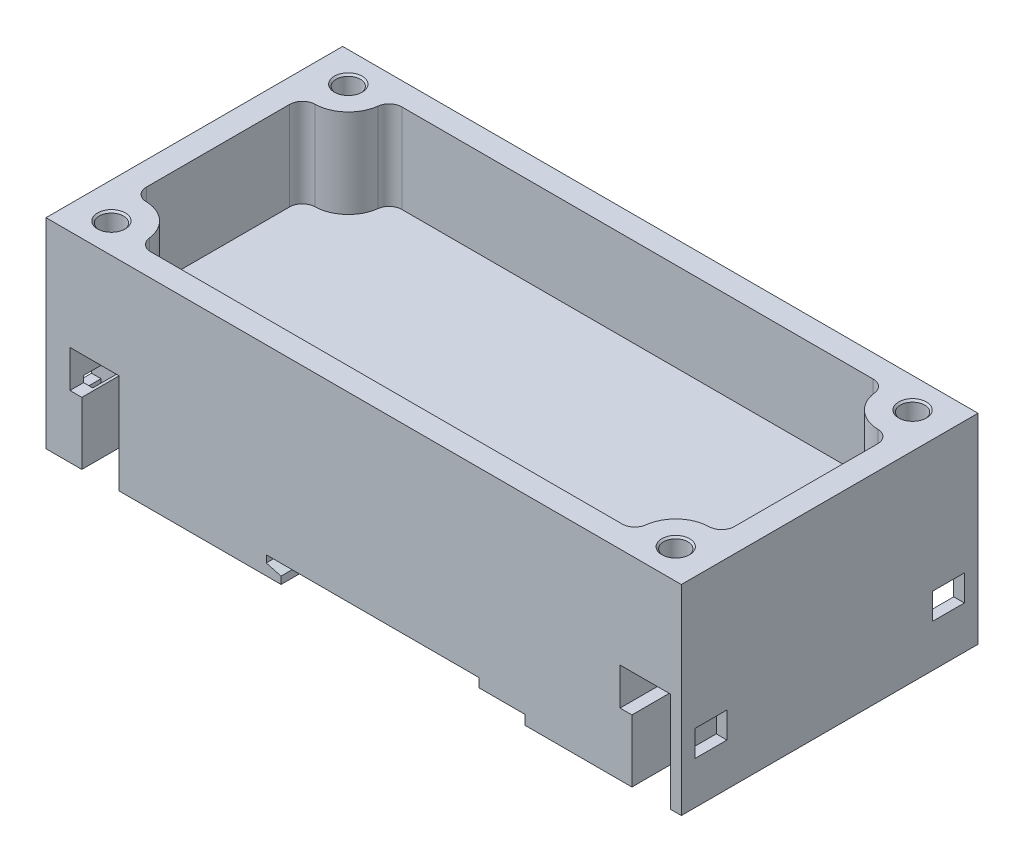
SolidWorks part; units mm, degrees
ref_plane "Front Plane" through (0, 0, 0) normal (0, 0, 1) x (1, 0, 0)
ref_plane "Top Plane" through (0, 0, 0) normal (0, 1, 0) x (1, 0, 0)
ref_plane "Right Plane" through (0, 0, 0) normal (1, 0, 0) x (0, 0, -1)
ref_plane "Plane1" through (0, 0, 0) normal (0, 0, 1) x (1, 0, 0)
sketch "Sketch1" plane through (0, 0, 0) normal (0, 0, 1) x (1, 0, 0)
  line L0 (-53.65, 33.8) -> (-53.65, 0)
  line L1 (-53.65, 0) -> (-47.6, 0)
  line L2 (-47.6, 0) -> (-47.6, 10.55)
  line L3 (-47.6, 10.55) -> (-49.6, 10.55)
  line L4 (-49.6, 10.55) -> (-49.6, 16.85)
  line L5 (-49.6, 16.85) -> (-41.3, 16.85)
  line L6 (-41.3, 16.85) -> (-41.3, 0)
  line L7 (-41.3, 0) -> (-13.95, 0)
  line L8 (-13.95, 0) -> (-13.95, 1.2301)
  line L9 (-13.95, 1.2301) -> (-16.45, 1.9)
  line L10 (-16.45, 1.9) -> (-16.45, 3.1)
  line L11 (-16.45, 3.1) -> (19.45, 3.1)
  line L12 (19.45, 3.1) -> (19.45, 1.6)
  line L13 (19.45, 1.6) -> (27.25, 1.6)
  line L14 (27.25, 1.6) -> (27.25, 0)
  line L15 (27.25, 0) -> (45.3, 0)
  line L16 (45.3, 0) -> (45.3, 10.55)
  line L17 (45.3, 10.55) -> (43.3, 10.55)
  line L18 (43.3, 10.55) -> (43.3, 16.85)
  line L19 (43.3, 16.85) -> (51.85, 16.85)
  line L20 (51.85, 16.85) -> (51.85, 0)
  line L21 (51.85, 0) -> (53.65, 0)
  line L22 (53.65, 0) -> (53.65, 33.8)
  line L23 (53.65, 33.8) -> (-53.65, 33.8)
extrude "Boss-Extrude1" add sketch "Sketch1" against normal blind 25.05 and the other way blind 25.05
ref_plane "Plane2" through (0, 0, 20) normal (0, 0, 1) x (1, 0, 0)
sketch "Sketch2" plane through (0, 0, 20) normal (0, 0, 1) x (1, 0, 0)
  line L0 (47.65, 33.8) -> (50, 33.8)
  line L1 (50, 33.8) -> (49.7, 33.5)
  line L2 (49.7, 33.5) -> (49.7, 26.6)
  line L3 (49.5, 26.4) -> (49.02, 26.4)
  line L4 (49.02, 26.4) -> (48.95, 18.4)
  line L5 (48.95, 18.4) -> (47.65, 18.4)
  line L6 (47.65, 18.4) -> (47.65, 33.8)
  line L7 (47.65, 18.4) -> (47.65, 33.8) construction
  arc A0 (49.7, 26.6) -> (49.5, 26.4) centre (49.5, 26.6) cw
revolve "Cut-Revolve1" cut sketch "Sketch2" angle 360 about L7 reverse direction yes
ref_plane "Plane3" through (0, 0, -20) normal (0, 0, 1) x (1, 0, 0)
sketch "Sketch3" plane through (0, 0, -20) normal (0, 0, 1) x (1, 0, 0)
  line L0 (47.65, 33.8) -> (50, 33.8)
  line L1 (50, 33.8) -> (49.7, 33.5)
  line L2 (49.7, 33.5) -> (49.7, 26.6)
  line L3 (49.5, 26.4) -> (49.02, 26.4)
  line L4 (49.02, 26.4) -> (48.95, 18.4)
  line L5 (48.95, 18.4) -> (47.65, 18.4)
  line L6 (47.65, 18.4) -> (47.65, 33.8)
  line L7 (47.65, 18.4) -> (47.65, 33.8) construction
  arc A0 (49.7, 26.6) -> (49.5, 26.4) centre (49.5, 26.6) cw
revolve "Cut-Revolve2" cut sketch "Sketch3" angle 360 about L7 reverse direction yes
ref_plane "Plane4" through (0, 0, -20) normal (0, 0, 1) x (1, 0, 0)
sketch "Sketch4" plane through (0, 0, -20) normal (0, 0, 1) x (1, 0, 0)
  line L0 (-47.65, 33.8) -> (-45.3, 33.8)
  line L1 (-45.3, 33.8) -> (-45.6, 33.5)
  line L2 (-45.6, 33.5) -> (-45.6, 26.6)
  line L3 (-45.8, 26.4) -> (-46.28, 26.4)
  line L4 (-46.28, 26.4) -> (-46.35, 18.4)
  line L5 (-46.35, 18.4) -> (-47.65, 18.4)
  line L6 (-47.65, 18.4) -> (-47.65, 33.8)
  line L7 (-47.65, 18.4) -> (-47.65, 33.8) construction
  arc A0 (-45.6, 26.6) -> (-45.8, 26.4) centre (-45.8, 26.6) cw
revolve "Cut-Revolve3" cut sketch "Sketch4" angle 360 about L7 reverse direction yes
ref_plane "Plane5" through (0, 0, 20) normal (0, 0, 1) x (1, 0, 0)
sketch "Sketch5" plane through (0, 0, 20) normal (0, 0, 1) x (1, 0, 0)
  line L0 (-47.65, 33.8) -> (-45.3, 33.8)
  line L1 (-45.3, 33.8) -> (-45.6, 33.5)
  line L2 (-45.6, 33.5) -> (-45.6, 26.6)
  line L3 (-45.8, 26.4) -> (-46.28, 26.4)
  line L4 (-46.28, 26.4) -> (-46.35, 18.4)
  line L5 (-46.35, 18.4) -> (-47.65, 18.4)
  line L6 (-47.65, 18.4) -> (-47.65, 33.8)
  line L7 (-47.65, 18.4) -> (-47.65, 33.8) construction
  arc A0 (-45.6, 26.6) -> (-45.8, 26.4) centre (-45.8, 26.6) cw
revolve "Cut-Revolve4" cut sketch "Sketch5" angle 360 about L7 reverse direction yes
ref_plane "Plane6" through (0, 33.8, 0) normal (0, 1, 0) x (1, 0, 0)
sketch "Sketch6" plane through (0, 33.8, 0) normal (0, 1, 0) x (1, 0, 0)
  line L0 (-39.8073, -21.2) -> (39.8073, -21.2)
  line L1 (49.65, -12.1014) -> (49.65, 12.1014)
  line L2 (39.8073, 21.2) -> (-39.8073, 21.2)
  line L3 (-49.65, 12.1014) -> (-49.65, -12.1014)
  arc A0 (-49.65, -12.1014) -> (-47.5408, -14.251) centre (-47.5, -12.1014) ccw
  arc A1 (-47.5408, -14.251) -> (-41.9417, -19.3085) centre (-47.65, -20) cw
  arc A2 (-41.9417, -19.3085) -> (-39.8073, -21.2) centre (-39.8073, -19.05) ccw
  arc A3 (39.8073, -21.2) -> (41.9417, -19.3085) centre (39.8073, -19.05) ccw
  arc A4 (41.9417, -19.3085) -> (47.5408, -14.251) centre (47.65, -20) cw
  arc A5 (47.5408, -14.251) -> (49.65, -12.1014) centre (47.5, -12.1014) ccw
  arc A6 (49.65, 12.1014) -> (47.5408, 14.251) centre (47.5, 12.1014) ccw
  arc A7 (47.5408, 14.251) -> (41.9417, 19.3085) centre (47.65, 20) cw
  arc A8 (41.9417, 19.3085) -> (39.8073, 21.2) centre (39.8073, 19.05) ccw
  arc A9 (-39.8073, 21.2) -> (-41.9417, 19.3085) centre (-39.8073, 19.05) ccw
  arc A10 (-41.9417, 19.3085) -> (-47.5408, 14.251) centre (-47.65, 20) cw
  arc A11 (-47.5408, 14.251) -> (-49.65, 12.1014) centre (-47.5, 12.1014) ccw
extrude "Cut-Extrude1" cut sketch "Sketch6" against normal blind 15
ref_plane "Plane7" through (53.65, 0, 0) normal (1, 0, 0) x (0, 0, -1)
sketch "Sketch7" plane through (53.65, 0, 0) normal (1, 0, 0) x (0, 0, -1)
  line L0 (17.35, 7.2) -> (22.75, 7.2)
  line L1 (22.75, 7.2) -> (22.75, 11.6)
  line L2 (22.75, 11.6) -> (17.35, 11.6)
  line L3 (17.35, 11.6) -> (17.35, 7.2)
extrude "Cut-Extrude2" cut sketch "Sketch7" against normal blind 3
ref_plane "Plane8" through (53.65, 0, 0) normal (1, 0, 0) x (0, 0, -1)
sketch "Sketch8" plane through (53.65, 0, 0) normal (1, 0, 0) x (0, 0, -1)
  line L0 (-22.75, 7.2) -> (-17.35, 7.2)
  line L1 (-17.35, 7.2) -> (-17.35, 11.6)
  line L2 (-17.35, 11.6) -> (-22.75, 11.6)
  line L3 (-22.75, 11.6) -> (-22.75, 7.2)
extrude "Cut-Extrude3" cut sketch "Sketch8" against normal blind 3
ref_plane "Plane9" through (-53.65, 0, 0) normal (1, 0, 0) x (0, 0, -1)
sketch "Sketch9" plane through (-53.65, 0, 0) normal (1, 0, 0) x (0, 0, -1)
  line L0 (17.35, 7.2) -> (22.75, 7.2)
  line L1 (22.75, 7.2) -> (22.75, 11.6)
  line L2 (22.75, 11.6) -> (17.35, 11.6)
  line L3 (17.35, 11.6) -> (17.35, 7.2)
extrude "Cut-Extrude4" cut sketch "Sketch9" along normal blind 5
ref_plane "Plane10" through (-53.65, 0, 0) normal (1, 0, 0) x (0, 0, -1)
sketch "Sketch10" plane through (-53.65, 0, 0) normal (1, 0, 0) x (0, 0, -1)
  line L0 (-22.75, 7.2) -> (-17.35, 7.2)
  line L1 (-17.35, 7.2) -> (-17.35, 11.6)
  line L2 (-17.35, 11.6) -> (-22.75, 11.6)
  line L3 (-22.75, 11.6) -> (-22.75, 7.2)
extrude "Cut-Extrude5" cut sketch "Sketch10" along normal blind 5
ref_plane "Plane11" through (-52.05, 0, 0) normal (1, 0, 0) x (0, 0, -1)
sketch "Sketch11" plane through (-52.05, 0, 0) normal (1, 0, 0) x (0, 0, -1)
  line L0 (-22.75, 6.2) -> (-17.35, 6.2)
  line L1 (-17.35, 6.2) -> (-17.35, 11.6)
  line L2 (-17.35, 11.6) -> (-22.75, 11.6)
  line L3 (-22.75, 11.6) -> (-22.75, 6.2)
extrude "Cut-Extrude6" cut sketch "Sketch11" along normal blind 4
ref_plane "Plane12" through (-52.05, 0, 0) normal (1, 0, 0) x (0, 0, -1)
sketch "Sketch12" plane through (-52.05, 0, 0) normal (1, 0, 0) x (0, 0, -1)
  line L0 (17.35, 6.2) -> (22.75, 6.2)
  line L1 (22.75, 6.2) -> (22.75, 11.6)
  line L2 (22.75, 11.6) -> (17.35, 11.6)
  line L3 (17.35, 11.6) -> (17.35, 6.2)
extrude "Cut-Extrude7" cut sketch "Sketch12" along normal blind 4
